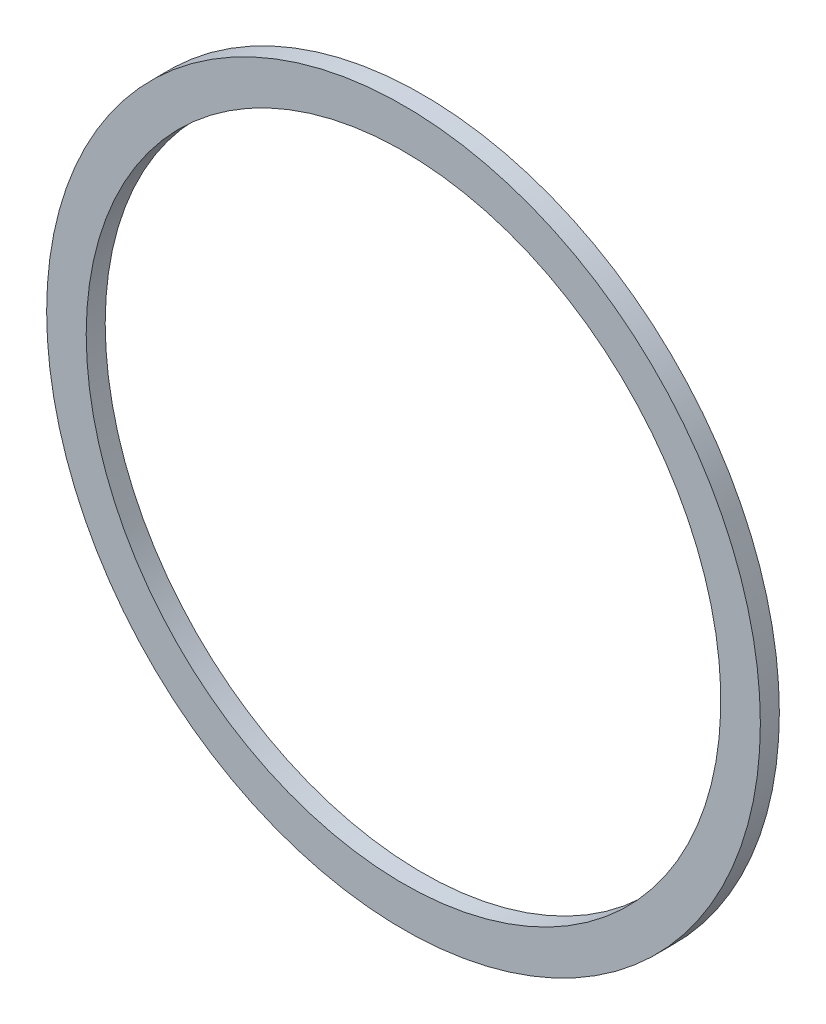
SolidWorks part; units mm, degrees
material "AISI 1020"
ref_plane "Front Plane" through (0, 0, 0) normal (0, 0, 1) x (1, 0, 0)
ref_plane "Top Plane" through (0, 0, 0) normal (0, 1, 0) x (1, 0, 0)
ref_plane "Right Plane" through (0, 0, 0) normal (1, 0, 0) x (0, 0, -1)
sketch "Sketch1" plane through (0, 0, 0) normal (0, 0, 1) x (1, 0, 0)
  circle A0 centre (0, 0) radius 50.927
  circle A1 centre (0, 0) radius 50.8 construction
  circle A2 centre (0, 0) radius 57.277
  dimension "D1" = 0.127
  dimension "D2" = 6.35
extrude "Boss-Extrude1" add sketch "Sketch1" along normal blind 3.048 contours A0 | A2 region at (0, 0, 0)
